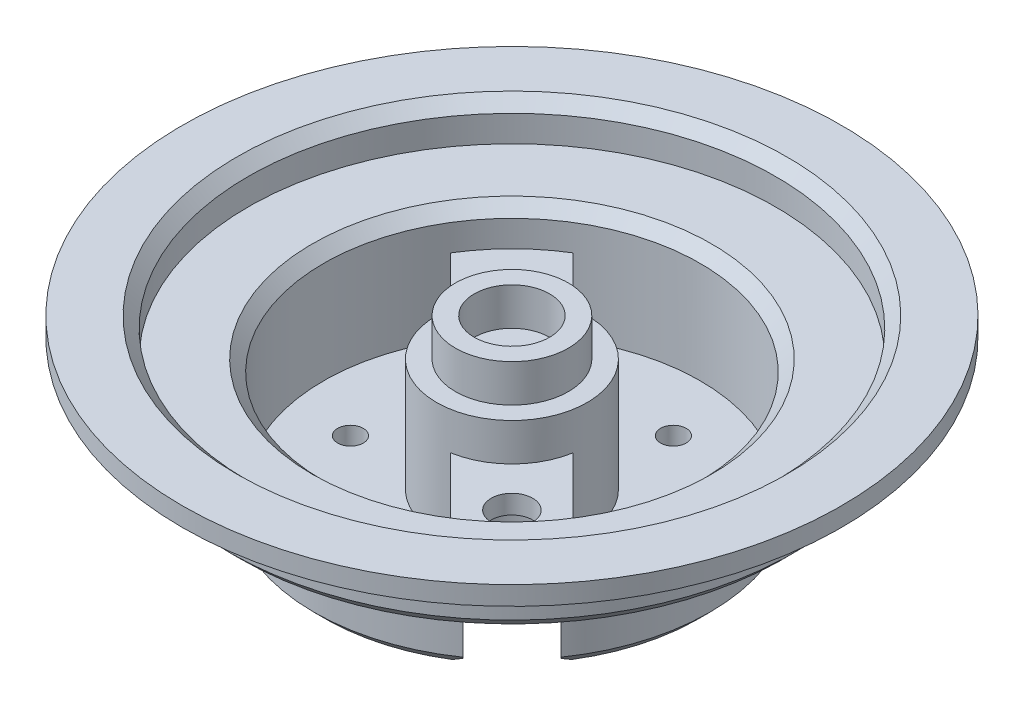
SolidWorks part; units mm, degrees
material "PBT General Purpose"
ref_plane "Front Plane" through (0, 0, 0) normal (0, 0, 1) x (1, 0, 0)
ref_plane "Top Plane" through (0, 0, 0) normal (0, 1, 0) x (1, 0, 0)
ref_plane "Right Plane" through (0, 0, 0) normal (1, 0, 0) x (0, 0, -1)
sketch "Sketch1" plane through (0, 0, 0) normal (0, 1, 0) x (1, 0, 0)
  circle A0 centre (0, 0) radius 75
  dimension "D1" = 150
extrude "Boss-Extrude1" add sketch "Sketch1" along normal blind 10
sketch "Sketch2" plane through (0, 10, 0) normal (0, 1, 0) x (1, 0, 0)
  circle A0 centre (0, 0) radius 70
  circle A2 centre (0, 0) radius 75
  circle A3 centre (0, 0) radius 75
  dimension "D2" = 140
  dimension "D1" = 0
extrude "Boss-Extrude2" add sketch "Sketch2" along normal blind 5
sketch "Sketch3" plane through (0, 15, 0) normal (0, 1, 0) x (1, 0, 0)
  circle A0 centre (0, 0) radius 87.5
  circle A1 centre (0, 0) radius 70
  dimension "D1" = 175
extrude "Boss-Extrude3" add sketch "Sketch3" along normal blind 5
sketch "Sketch4" plane through (0, 10, 0) normal (0, 1, 0) x (1, 0, 0)
  circle A0 centre (0, 0) radius 15
  dimension "D1" = 30
extrude "Boss-Extrude4" add sketch "Sketch4" along normal blind 10
sketch "Sketch5" plane through (0, 20, 0) normal (0, 1, 0) x (1, 0, 0)
  circle A0 centre (0, 0) radius 4
  dimension "D1" = 8
extrude "Cut-Extrude1" cut sketch "Sketch5" against normal through all
sketch "Sketch9" plane through (0, 0, 0) normal (0, -1, 0) x (1, 0, 0)
  circle A0 centre (0, 0) radius 17.5
  circle A1 centre (0, 0) radius 52.5
  dimension "D1" = 35
  dimension "D2" = 105
extrude "Boss-Extrude6" add sketch "Sketch9" along normal blind 25
sketch "Sketch10" plane through (0, 10, 0) normal (0, 1, 0) x (1, 0, 0)
  circle A0 centre (0, 0) radius 20
  circle A1 centre (0, 0) radius 50
  dimension "D1" = 100
  dimension "D2" = 40
extrude "Cut-Extrude5" cut sketch "Sketch10" against normal blind 30
sketch "Sketch6" plane through (0, -20, 0) normal (0, 1, 0) x (1, 0, 0)
  line L0 (0, 0) -> (24.7487, -24.7487) construction
  line L1 (24.7487, -24.7487) -> (33.8074, 9.0587) construction
  line L2 (33.8074, 9.0587) -> (9.0587, 33.8074) construction
  line L3 (9.0587, 33.8074) -> (-24.7487, 24.7487) construction
  line L4 (-24.7487, 24.7487) -> (-33.8074, -9.0587) construction
  line L5 (-33.8074, -9.0587) -> (-9.0587, -33.8074) construction
  line L6 (-9.0587, -33.8074) -> (24.7487, -24.7487)
  line L7 (0, 0) -> (87.5, 0) construction
  circle A0 centre (0, 0) radius 35 construction
  circle A1 centre (0, 35) radius 3 construction
  circle A2 centre (35, 0) radius 3 construction
  circle A3 centre (-35, 0) radius 3 construction
  circle A4 centre (0, -35) radius 3 construction
  circle A5 centre (0, 0) radius 30.3109 construction
  circle A6 centre (0, 0) radius 87.5 construction
  circle A7 centre (9.0587, 33.8074) radius 3.4
  circle A8 centre (33.8074, 9.0587) radius 3.4
  circle A9 centre (-9.0587, -33.8074) radius 3.4
  circle A10 centre (-33.8074, -9.0587) radius 3.4
  dimension "D1" = 70
  dimension "D2" = 6
  dimension "D4" = 6.8
  dimension "D3" = 45
sketch "Sketch11" plane through (0, 20, 0) normal (0, 1, 0) x (1, 0, 0)
  circle A0 centre (0, 0) radius 10
  dimension "D1" = 20
extrude "Cut-Extrude7" cut sketch "Sketch11" against normal blind 10
extrude "Cut-Extrude10" cut sketch "Sketch6" against normal blind 20 contours A10 | A7 | A8 | A9 region at (9.0587, -20, -33.8074) region at (33.8074, -20, -9.0587) region at (-12.3342, -20, 34.2386) region at (-33.8074, -20, 9.0587)
sketch "Sketch15" plane through (0, -20, 0) normal (0, 1, 0) x (1, 0, 0)
  line L0 (-44.3533, 28.0898) -> (-28.0898, 44.3533)
  line L1 (-44.3533, 28.0898) -> (-19.7022, 3.4387)
  line L2 (-28.0898, 44.3533) -> (-3.4387, 19.7022)
  line L3 (-19.7022, 3.4387) -> (-3.4387, 19.7022)
  line L4 (19.7022, -3.4387) -> (3.4387, -19.7022)
  line L5 (19.7022, -3.4387) -> (44.3533, -28.0898)
  line L6 (3.4387, -19.7022) -> (28.0898, -44.3533)
  line L7 (44.3533, -28.0898) -> (28.0898, -44.3533)
  line L8 (0, 0) -> (61.8718, -61.8718) construction
  line L9 (0, 0) -> (87.5, 0) construction
  circle A0 centre (0, 0) radius 52.5 construction
  circle A1 centre (0, 0) radius 20 construction
  circle A2 centre (0, 0) radius 87.5 construction
  dimension "D1" = 45
  dimension "D2" = 23
extrude "Boss-Extrude8" add sketch "Sketch15" along normal blind 20
sketch "Sketch16" plane through (0, 0, 0) normal (0, 1, 0) x (1, 0, 0)
  line L0 (-24.7487, 24.7487) -> (24.7487, -24.7487) construction
  line L1 (0, 0) -> (87.5, 0) construction
  circle A0 centre (0, 0) radius 87.5 construction
  circle A1 centre (-24.7487, 24.7487) radius 5.5
  circle A2 centre (24.7487, -24.7487) radius 5.5
  dimension "D3" = 11
  dimension "D4" = 11
  dimension "D1" = 45
  dimension "D2" = 70
extrude "Cut-Extrude11" cut sketch "Sketch16" against normal through all
sketch "Sketch17" plane through (0, -25, 0) normal (0, -1, 0) x (1, 0, 0)
  line L0 (-24.7487, -24.7487) -> (0, 0) construction
  line L1 (-24.7487, -11.7487) -> (-83.4674, -70.4674)
  line L2 (-11.7487, -24.7487) -> (-77.0623, -90.0623)
  line L3 (-77.0623, -90.0623) -> (-83.4674, -70.4674)
  line L4 (0, 0) -> (-82.7774, 82.7774) construction
  line L5 (90.0623, 77.0623) -> (70.4674, 83.4674)
  line L6 (24.7487, 11.7487) -> (90.0623, 77.0623)
  line L7 (11.7487, 24.7487) -> (70.4674, 83.4674)
  arc A1 (-11.7487, -24.7487) -> (-24.7487, -11.7487) centre (-24.7487, -24.7487) ccw
  arc A2 (24.7487, 11.7487) -> (11.7487, 24.7487) centre (24.7487, 24.7487) cw
  dimension "D1" = 26
extrude "Cut-Extrude12" cut sketch "Sketch17" against normal blind 20
chamfer "Chamfer2" distance 2 angle 45 6 edges at (33.8992, -25, 20.8992) (15.5563, -25, 15.5563) (20.8992, -25, 33.8992) (-33.8992, -25, -20.8992) (-15.5563, -25, -15.5563) (-20.8992, -25, -33.8992)
chamfer "Chamfer3" distance 3 angle 45 5 edges at (-37.1231, -25, 37.1231) (37.1231, -25, -37.1231) (0, 0, 75) (0, 10, 50) (0, 20, 70)
